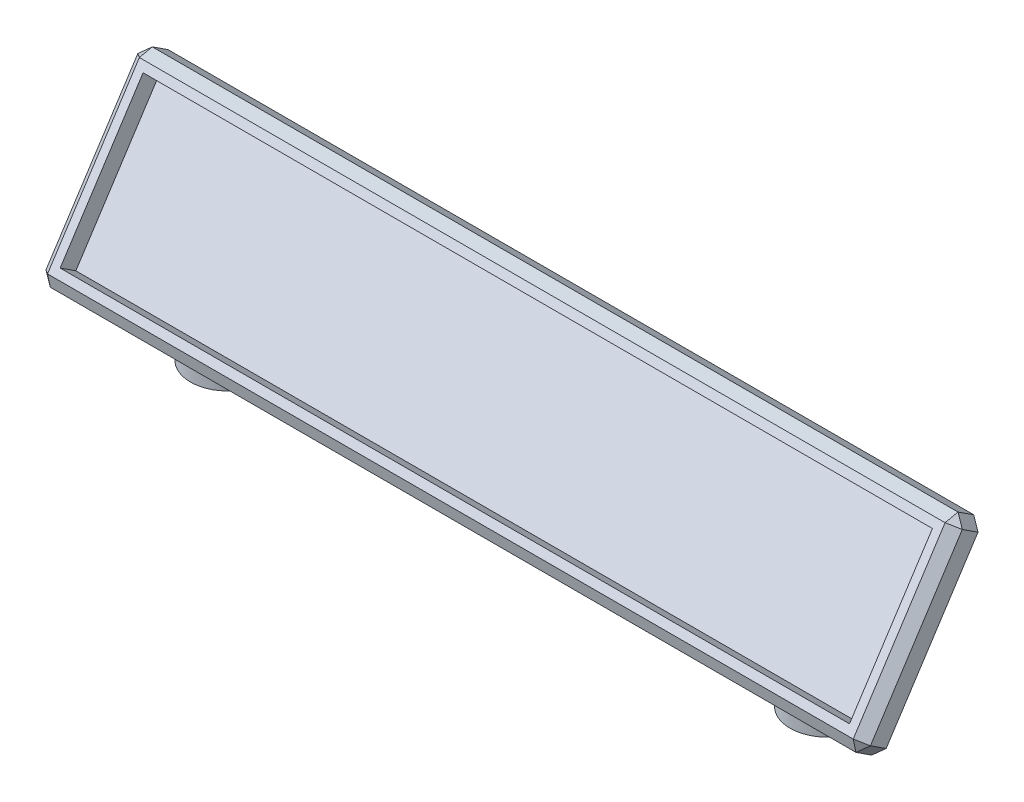
SolidWorks part; units mm, degrees
note: '?' marks a value the reader was unsure of.
ref_plane "Front Plane" through (0, 0, 0) normal (0, 0, 1) x (1, 0, 0)
ref_plane "Top Plane" through (0, 0, 0) normal (0, 1, 0) x (1, 0, 0)
ref_plane "Right Plane" through (0, 0, 0) normal (1, 0, 0) x (0, 0, -1)
sketch "Sketch2" plane through (0, 0, 0) normal (0, 1, 0) x (1, 0, 0)
  line L0 (50.8, 0) -> (-50.8, 0) construction
  circle A0 centre (-50.8, 0) radius 6.35
  circle A1 centre (50.8, 0) radius 6.35
  point P8 (0, 0)
  dimension "D2" = 12.7
  dimension "D1" = 101.6
extrude "Boss-Extrude1" add sketch "Sketch2" along normal blind 19.05
ref_plane "Plane1" through (0, 19.05, 0) normal (0, 1, 0) x (1, 0, 0)
ref_axis "Axis1" through (88.99, 19.05, 0) along (-1, 0, 0)?
ref_plane "Plane2" through (0, 5.6508, 8.7015) normal (0, 0.5446, 0.8387) x (-1, 0, 0)
sketch "Sketch3" plane through (0, 5.6508, 8.7015) normal (0, 0.5446, 0.8387) x (-1, 0, 0)
  line L0 (-50.8, -15.9767) -> (50.8, -15.9767)
  line L2 (-69.85, -31.8517) -> (69.85, -31.8517)
  line L3 (-69.85, -31.8517) -> (-69.85, -0.1017)
  line L4 (-69.85, -0.1017) -> (69.85, -0.1017)
  line L5 (69.85, -31.8517) -> (69.85, -0.1017)
  line L6 (-69.85, -31.8517) -> (69.85, -0.1017) construction
  line L7 (-69.85, -0.1017) -> (69.85, -31.8517) construction
  ellipse E0 centre (50.8, -15.9767) end of major axis (44.45, -15.9767) minor radius 3.4585 construction
  ellipse E1 centre (-50.8, -15.9767) end of major axis (-57.15, -15.9767) minor radius 3.4585 construction
  ellipse E2 centre (50.8, -15.9767) end of major axis (44.45, -15.9767) minor radius 3.4585 construction
  ellipse E3 centre (-50.8, -15.9767) end of major axis (-57.15, -15.9767) minor radius 3.4585 construction
  point P22 (0, -15.9767)
  dimension "D1" = 139.7
  dimension "D2" = 31.75
extrude "Boss-Extrude2" add sketch "Sketch3" along normal blind 6.35
sketch "Sketch8" plane through (0, 19.05, 0) normal (0, 1, 0) x (1, 0, 0)
  line L0 (44.45, 0) -> (57.15, 0) construction
  line L1 (-57.15, 0) -> (-44.45, 0) construction
  line L2 (44.45, 0) -> (57.15, 0)
  line L3 (-57.15, 0) -> (-44.45, 0)
  arc A0 (57.15, 0) -> (44.45, 0) centre (50.8, 0) ccw construction
  arc A1 (-44.45, 0) -> (-57.15, 0) centre (-50.8, 0) ccw construction
  arc A2 (57.15, 0) -> (44.45, 0) centre (50.8, 0) ccw
  arc A3 (-44.45, 0) -> (-57.15, 0) centre (-50.8, 0) ccw
extrude "Boss-Extrude3" add sketch "Sketch8" along normal up to next contours L2 A2 | A3 L3
sketch "Sketch9" plane through (0, 9.1093, 14.0271) normal (0, 0.5446, 0.8387) x (1, 0, 0)
  line L8 (66.875, 28.8767) -> (-66.875, 28.8767)
  line L9 (-66.875, 28.8767) -> (-66.875, 3.0767)
  line L10 (-66.875, 3.0767) -> (66.875, 3.0767)
  line L11 (66.875, 3.0767) -> (66.875, 28.8767)
  line L12 (66.875, 28.8767) -> (-66.875, 28.8767)
  line L13 (-66.875, 28.8767) -> (-66.875, 3.0767)
  line L14 (-66.875, 3.0767) -> (66.875, 3.0767)
  line L15 (66.875, 3.0767) -> (66.875, 28.8767)
  dimension "D1" = 2.975
extrude "Cut-Extrude1" cut sketch "Sketch9" against normal blind 3.175
chamfer "Chamfer2" distance 1.5875 angle 45 12 edges at (-69.85, 19.05, 0) (0, 32.3639, -8.6461) (69.85, 19.05, 0) (0, 5.7361, 8.6461) (0, 9.1946, 13.9717) (-69.85, 7.4653, 11.3089) (-69.85, 22.5085, 5.3256) (69.85, 7.4653, 11.3089) (69.85, 22.5085, 5.3256) (69.85, 34.0931, -5.9834) (0, 35.8224, -3.3206) (-69.85, 34.0931, -5.9834)
hole_wizard "Hole1" positions "3DSketch1" profile "Sketch10" legacy
sketch3d "3DSketch1"
  line L0 (-50.8, 28.8281, 0) -> (-50.8, 0, 0) construction
  line L1 (50.8, 28.8281, 0) -> (50.8, 0, 0) construction
  point P0 (-50.8, 0, 0)
  point P4 (50.8, 0, 0)
sketch "Sketch10" plane through (-50.8, 0, 0) normal (1, 0, 0) x (0, 0, -1)
  line L0 (0, 0) -> (0, 10.16)
  line L1 (0, 10.16) -> (2.54, 10.16)
  line L2 (2.54, 10.16) -> (2.54, 0.6858)
  line L3 (2.54, 0.6858) -> (3.175, 0.6858)
  line L4 (3.175, 0.6858) -> (3.175, 0)
  line L5 (3.175, 0) -> (0, 0)
  line L6 (0, 110) -> (0, -10) construction
  dimension "Diameter" = 5.08
  dimension "Depth" = 10.16
  dimension "C-Bore Diameter" = 6.35
  dimension "C-Bore Depth" = 0.6858
